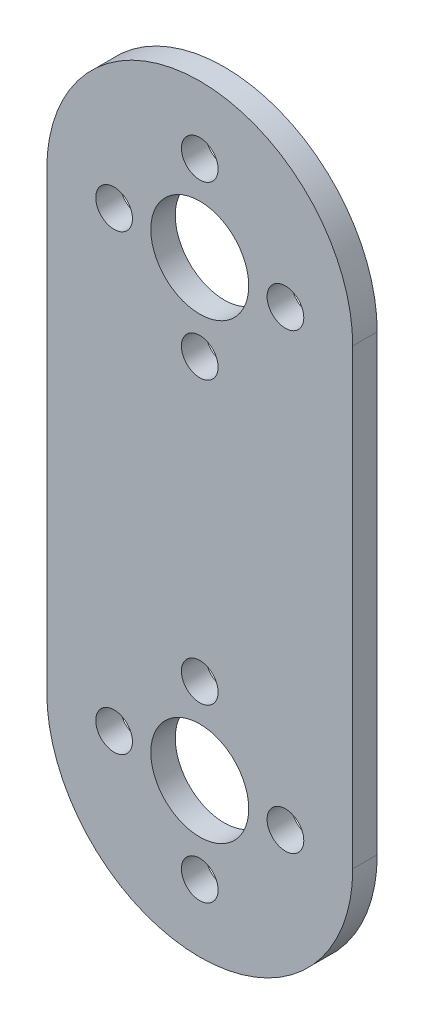
SolidWorks part; units mm, degrees
material "6063-T4"
ref_plane "Front Plane" through (0, 0, 0) normal (0, 0, 1) x (1, 0, 0)
ref_plane "Top Plane" through (0, 0, 0) normal (0, 1, 0) x (1, 0, 0)
ref_plane "Right Plane" through (0, 0, 0) normal (1, 0, 0) x (0, 0, -1)
sketch "Sketch1" plane through (0, 0, 0) normal (0, 0, 1) x (1, 0, 0)
  line L0 (0, 0) -> (0, 37) construction
  line L1 (-12.5, 0) -> (-12.5, 37)
  line L2 (12.5, 0) -> (12.5, 37)
  arc A0 (-12.5, 0) -> (12.5, 0) centre (0, 0) ccw
  arc A1 (12.5, 37) -> (-12.5, 37) centre (0, 37) ccw
  point P3 (0, 18.5)
  point P8 (0, 49.5)
  point P9 (0, -12.5)
  dimension "D1" = 62
  dimension "D2" = 25
extrude "Boss-Extrude1" add sketch "Sketch1" along normal mid plane 2
sketch "Sketch2" plane through (0, 0, -1) normal (0, 0, -1) x (-1, 0, 0)
  line L0 (37.5, 18.5) -> (-12.5, 18.5)
  line L1 (12.5, 37) -> (12.5, 0) construction
  line L2 (-12.5, 0) -> (-12.5, 37) construction
  circle A0 centre (0, 37) radius 4
  circle A1 centre (0, 37) radius 7 construction
  circle A2 centre (0, 44) radius 1.5
  point P3 (12.5, 18.5)
  dimension "D1" = 3
  dimension "D2" = 14
  dimension "D3" = 8
  dimension "D4" = 25
extrude "Cut-Extrude1" cut sketch "Sketch2" against normal up to next contours A0 region at (0, 37, -1)
extrude "Cut-Extrude2" cut sketch "Sketch2<3>" against normal up to next contours A2 region at (0, 44, -1)
sketch "Sketch2<3>" plane through (0, 0, -1) normal (0, 0, -1) x (-1, 0, 0) same geometry as "Sketch2"
pattern_circular "CirPattern1" count 4 over 360 about axis through (0, 37, -1) along (0, 0, -1) of "Cut-Extrude2"
sketch "Sketch3" plane through (0, 0, -1) normal (0, 0, -1) x (-1, 0, 0)
  line L0 (44.3557, 18.5) -> (-19.3557, 18.5)
  point P3 (12.5, 18.5)
ref_plane "Plane1" through (0, 18.5, 0) normal (0, 1, 0) x (1, 0, 0)
mirror "Mirror1" about plane through (0, 18.5, 0) normal (0, 1, 0) of "CirPattern1", "Cut-Extrude2", "Cut-Extrude1"
